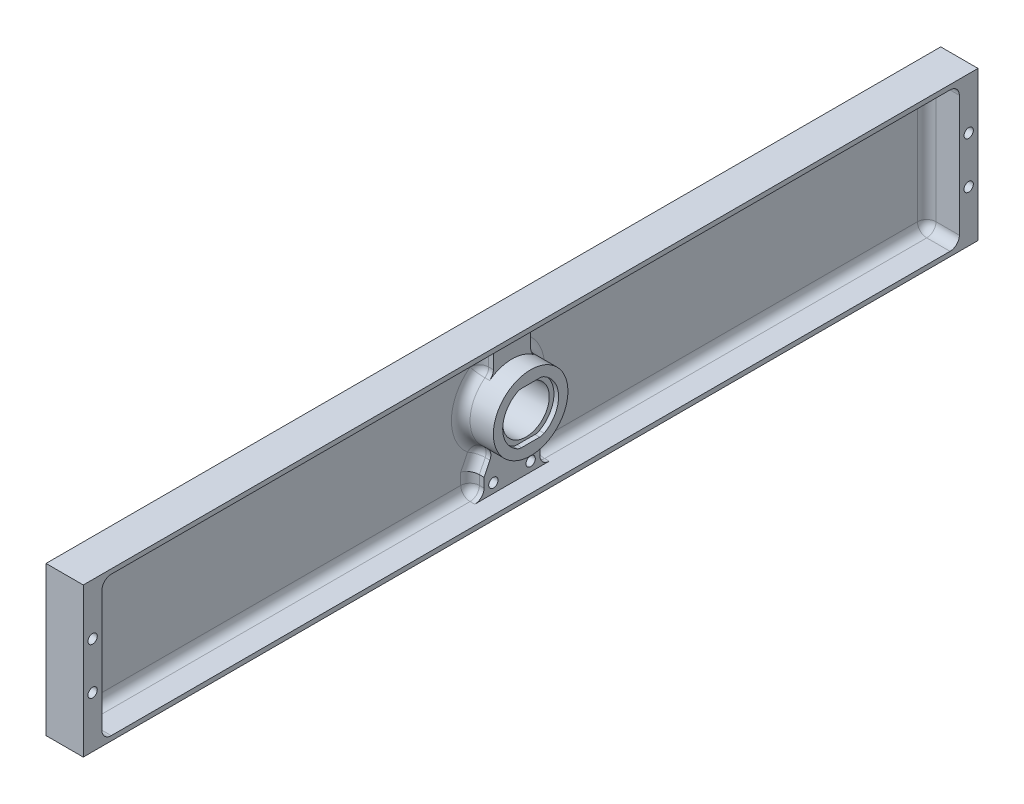
SolidWorks part; units mm, degrees
material "6061 Alloy"
ref_plane "Front Plane" through (0, 0, 0) normal (0, 0, 1) x (1, 0, 0)
ref_plane "Top Plane" through (0, 0, 0) normal (0, 1, 0) x (1, 0, 0)
ref_plane "Right Plane" through (0, 0, 0) normal (1, 0, 0) x (0, 0, -1)
sketch "Sketch1" plane through (0, 0, 0) normal (0, 0, 1) x (1, 0, 0)
  line L0 (25.4, 101.6) -> (25.4, 98.425)
  line L1 (0, 0) -> (25.4, 0)
  line L2 (0, 0) -> (0, 101.6)
  line L3 (0, 101.6) -> (25.4, 101.6)
  line L4 (25.4, 98.425) -> (3.175, 98.425)
  line L5 (3.175, 98.425) -> (3.175, 3.175)
  line L6 (3.175, 3.175) -> (25.4, 3.175)
  line L7 (25.4, 3.175) -> (25.4, 0)
  line L8 (0, 50.8) -> (3.175, 50.8) construction
  dimension "D1" = 101.6
  dimension "D2" = 25.4
  dimension "D3" = 3.175
extrude "Channel" add sketch "Sketch1" along normal mid plane 609.6
sketch "Sketch7" plane through (0, 0, 0) normal (-1, 0, 0) x (0, 0, 1)
  line L0 (304.8, 0) -> (-304.8, 0) construction
  line L1 (304.8, 101.6) -> (292.1, 101.6)
  line L2 (304.8, 101.6) -> (304.8, 0)
  line L3 (304.8, 0) -> (292.1, 0)
  line L4 (292.1, 101.6) -> (292.1, 0)
  line L5 (304.8, 101.6) -> (-304.8, 101.6) construction
  line L6 (-304.8, 0) -> (-292.1, 0)
  line L7 (-304.8, 0) -> (-304.8, 101.6)
  line L8 (-304.8, 101.6) -> (-292.1, 101.6)
  line L9 (-292.1, 0) -> (-292.1, 101.6)
  dimension "D1" = 12.7
extrude "Boss-Extrude4" add sketch "Sketch7" against normal through all
sketch "Sketch2" plane through (0, 0, 0) normal (-1, 0, 0) x (0, 0, 1)
  line L0 (0, 0) -> (0, 101.6) construction
  line L1 (304.8, 101.6) -> (-304.8, 101.6) construction
  circle A0 centre (0, 50.8) radius 15.875
  circle A1 centre (0, 50.8) radius 25.4
  dimension "D1" = 31.75
  dimension "D2" = 50.8
extrude "Mounting Boss" add sketch "Sketch2" against normal blind 25.4
sketch "Sketch4" plane through (0, 0, 0) normal (-1, 0, 0) x (0, 0, 1)
  line L2 (304.8, 101.6) -> (-304.8, 101.6) construction
  line L3 (12.7, 101.6) -> (-12.7, 101.6)
  line L4 (12.7, 101.6) -> (12.7, 28.803)
  line L5 (19.05, 3.175) -> (-19.05, 3.175)
  line L6 (-12.7, 101.6) -> (-12.7, 28.803)
  line L8 (-19.05, 3.175) -> (-19.05, 15.875)
  line L9 (19.05, 3.175) -> (19.05, 15.875)
  line L10 (292.1, 3.175) -> (-292.1, 3.175) construction
  line L11 (19.05, 15.875) -> (12.7, 28.803)
  line L12 (-12.7, 28.803) -> (-19.05, 15.875)
  circle A2 centre (0, 50.8) radius 15.875 construction
  circle A4 centre (0, 50.8) radius 25.4 construction
  point P9 (0, 3.175)
  point P12 (0, 50.8)
  point P20 (0, 101.6)
  dimension "D1" = 25.4
  dimension "D2" = 38.1
  dimension "D3" = 12.7
extrude "Mount Support" add sketch "Sketch4" against normal blind 12.7
sketch "Sketch3" plane through (0, 0, 0) normal (1, 0, 0) x (0, 0, -1)
  circle A0 centre (0, 50.8) radius 15.875 construction
  circle A1 centre (0, 50.8) radius 15.875
extrude "Bore" cut sketch "Sketch3" along normal through all
sketch "Sketch5" plane through (25.4, 0, 0) normal (1, 0, 0) x (0, 0, -1)
  line L0 (6.1484, 68.2625) -> (-6.1484, 68.2625)
  line L1 (6.1484, 33.3375) -> (-6.1484, 33.3375)
  arc A0 (9.2225, 67.4688) -> (9.2225, 34.1313) centre (0, 50.8) cw
  circle A1 centre (0, 50.8) radius 15.875 construction
  arc A2 (-9.2225, 67.4688) -> (-9.2225, 34.1313) centre (0, 50.8) ccw
  arc A3 (-6.1484, 33.3375) -> (-9.2225, 34.1313) centre (-6.1484, 39.6875) cw
  arc A4 (9.2225, 34.1313) -> (6.1484, 33.3375) centre (6.1484, 39.6875) cw
  arc A5 (9.2225, 67.4688) -> (6.1484, 68.2625) centre (6.1484, 61.9125) ccw
  arc A6 (-6.1484, 68.2625) -> (-9.2225, 67.4688) centre (-6.1484, 61.9125) ccw
  dimension "D1" = 19.05
  dimension "D3" = 6.35
  dimension "D2" = 34.925
extrude "Key Cut" cut sketch "Sketch5" against normal blind 3.175
sketch "Sketch6" plane through (0, 0, 0) normal (-1, 0, 0) x (0, 0, 1)
  line L0 (304.8, 50.8) -> (298.45, 50.8) construction
  line L1 (304.8, 101.6) -> (304.8, 0) construction
  line L2 (298.45, 34.925) -> (298.45, 66.675) construction
  line L3 (0, 0) -> (0, 101.6) construction
  line L4 (304.8, 101.6) -> (-304.8, 101.6) construction
  circle A0 centre (298.45, 66.675) radius 3.175
  circle A1 centre (298.45, 34.925) radius 3.175
  circle A2 centre (-298.45, 34.925) radius 3.175
  circle A3 centre (-298.45, 66.675) radius 3.175
  dimension "D3" = 6.35
  dimension "D1" = 31.75
  dimension "D2" = 6.35
extrude "Cut-Extrude3" cut sketch "Sketch6" against normal through all
sketch "Sketch8" plane through (0, 0, 0) normal (-1, 0, 0) x (0, 0, 1)
  line L1 (-171.45, 98.425) -> (-133.35, 98.425)
  line L2 (-171.45, 98.425) -> (-171.45, 85.725)
  line L3 (-171.45, 85.725) -> (-133.35, 85.725)
  line L4 (-133.35, 98.425) -> (-133.35, 85.725)
  line L6 (133.35, 98.425) -> (171.45, 98.425)
  line L7 (133.35, 98.425) -> (133.35, 85.725)
  line L8 (133.35, 85.725) -> (171.45, 85.725)
  line L9 (171.45, 98.425) -> (171.45, 85.725)
  line L10 (-12.7, 98.425) -> (-292.1, 98.425) construction
  point P16 (-152.4, 98.425)
  point P18 (152.4, 98.425)
  dimension "D1" = 12.7
  dimension "D2" = 38.1
  dimension "D3" = 152.4
  dimension "D4" = 152.4
extrude "Boss-Extrude5" add sketch "Sketch8" against normal blind 12.7
fillet "Fillet4" radius 6.35 38 edges at (3.175, 50.8, -292.1) (3.175, 3.175, -155.575) (3.175, 9.525, -19.05) (3.175, 22.339, -15.875) (3.175, 50.8, -25.4) (3.175, 85.611, -12.7) (3.175, 98.425, -73.025) (3.175, 92.075, -133.35) (3.175, 85.725, -152.4) (3.175, 92.075, -171.45) (3.175, 98.425, -231.775) (3.175, 85.611, 12.7) (3.175, 50.8, 25.4) (3.175, 22.339, 15.875) (3.175, 9.525, 19.05) (3.175, 3.175, 155.575) (3.175, 50.8, 292.1) (3.175, 98.425, 231.775) (3.175, 92.075, 171.45) (3.175, 85.725, 152.4) (3.175, 92.075, 133.35) (3.175, 98.425, 73.025) (7.9375, 3.175, 19.05) (7.9375, 28.803, 12.7) (7.9375, 72.797, 12.7) (7.9375, 72.797, -12.7) (7.9375, 28.803, -12.7) (7.9375, 3.175, -19.05) (14.2875, 3.175, -292.1) (14.2875, 98.425, -292.1) (7.9375, 98.425, -171.45) (7.9375, 98.425, -133.35) (7.9375, 98.425, -12.7) (7.9375, 98.425, 12.7) (7.9375, 98.425, 133.35) (7.9375, 98.425, 171.45) (14.2875, 3.175, 292.1) (14.2875, 98.425, 292.1)
sketch "Sketch9" plane through (0, 0, 0) normal (-1, 0, 0) x (0, 0, 1)
  line L0 (-165.1, 92.075) -> (-139.7, 92.075) construction
  line L1 (139.7, 92.075) -> (165.1, 92.075) construction
  line L2 (-12.7, 9.525) -> (12.7, 9.525) construction
  line L3 (0, 0) -> (0, 9.525) construction
  line L4 (152.4, 92.075) -> (152.4, 101.6) construction
  line L5 (304.8, 101.6) -> (-304.8, 101.6) construction
  line L6 (-152.4, 92.075) -> (-152.4, 101.6) construction
  circle A0 centre (-165.1, 92.075) radius 3.175
  circle A1 centre (-139.7, 92.075) radius 3.175
  circle A2 centre (-12.7, 9.525) radius 3.175
  circle A3 centre (12.7, 9.525) radius 3.175
  circle A4 centre (165.1, 92.075) radius 3.175
  circle A5 centre (139.7, 92.075) radius 3.175
  point P6 (0, 9.525)
  point P7 (152.4, 92.075)
  point P9 (-152.4, 92.075)
  dimension "D5" = 6.35
  dimension "D1" = 25.4
  dimension "D2" = 9.525
  dimension "D3" = 152.4
  dimension "D4" = 152.4
extrude "Cut-Extrude4" cut sketch "Sketch9" against normal through all
